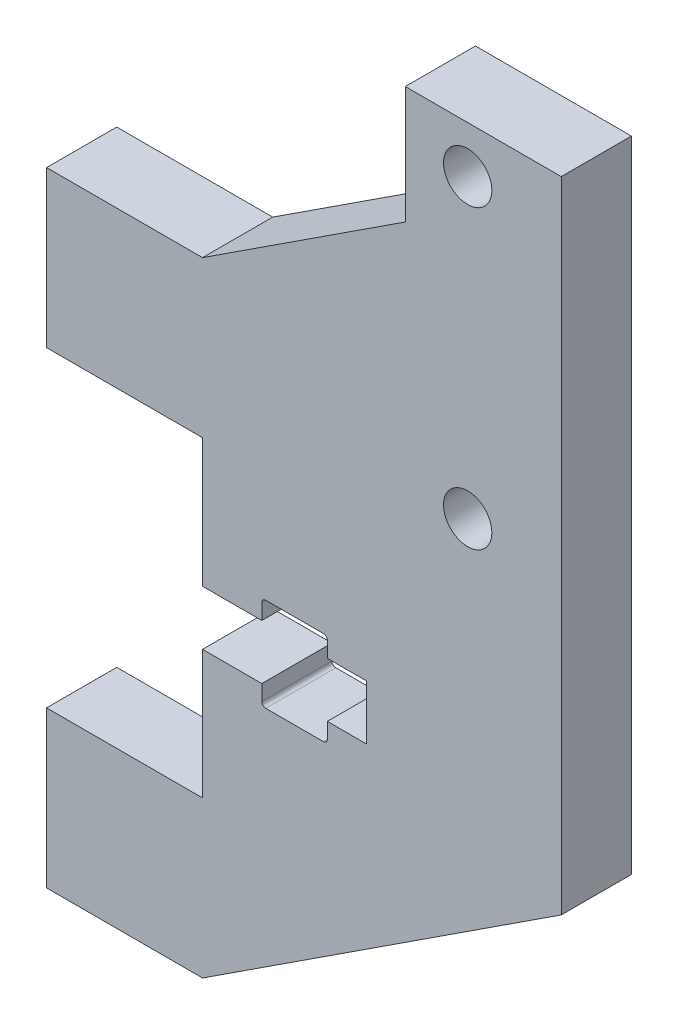
SolidWorks part; units mm, degrees
ref_plane "Front Plane" through (0, 0, 0) normal (0, 0, 1) x (1, 0, 0)
ref_plane "Top Plane" through (0, 0, 0) normal (0, 1, 0) x (1, 0, 0)
ref_plane "Right Plane" through (0, 0, 0) normal (1, 0, 0) x (0, 0, -1)
sketch "Sketch1" plane through (0, 0, 0) normal (0, 0, 1) x (1, 0, 0)
  line L0 (13, 3.4783) -> (0, -5)
  line L1 (0, -5) -> (-10, -5)
  line L2 (-10, -5) -> (-10, -15)
  line L3 (-10, -15) -> (0, -15)
  line L4 (0, -15) -> (0, -35)
  line L5 (0, -35) -> (-10, -35)
  line L6 (-10, -35) -> (-10, -45)
  line L7 (-10, -45) -> (0, -45)
  line L10 (0, -45) -> (23, -30)
  line L11 (23, -30) -> (23, 11)
  line L12 (23, 11) -> (13, 11)
  line L13 (13, 11) -> (13, 3.4783)
  line L15 (0, -5) -> (0, -45) construction
  line L16 (-10, -10) -> (0, -10) construction
  line L17 (-10, -40) -> (0, -40) construction
  line L18 (-10, -15) -> (-10, -35) construction
  line L19 (-10, -25) -> (0, -25) construction
  dimension "D2" = 10
  dimension "D3" = 10
  dimension "D4" = 10
  dimension "D5" = 15
  dimension "D8" = 10
  dimension "D10" = 13
  dimension "D6" = 15
  dimension "D7" = 16
extrude "Boss-Extrude1" add sketch "Sketch1" along normal blind 4.5
sketch "Sketch2" plane through (0, 0, 4.5) normal (0, 0, 1) x (1, 0, 0)
  line L0 (0, -25) -> (23, -25) construction
  line L1 (0, -15) -> (0, -35) construction
  line L3 (10.5, -26.75) -> (10.5, -23.25) construction
  line L4 (10.5, -23.25) -> (0, -23.25) construction
  line L5 (0, -26.75) -> (0, -23.25)
  line L6 (0, -23.25) -> (3.8, -23.25)
  line L7 (3.8, -23.25) -> (3.8, -22.25)
  line L8 (4.05, -22) -> (7.75, -22)
  line L9 (8, -22.25) -> (8, -23.25)
  line L10 (8, -23.25) -> (10.5, -23.25)
  line L11 (10.5, -23.25) -> (10.5, -26.75)
  line L12 (10.5, -26.75) -> (0, -26.75) construction
  line L13 (8, -26.75) -> (10.5, -26.75)
  line L14 (8, -27.75) -> (8, -26.75)
  line L15 (4.05, -28) -> (7.75, -28)
  line L16 (3.8, -26.75) -> (3.8, -27.75)
  line L17 (0, -26.75) -> (3.8, -26.75)
  line L18 (23, -30) -> (23, 11) construction
  arc A0 (7.75, -22) -> (8, -22.25) centre (7.75, -22.25) cw
  arc A1 (3.8, -22.25) -> (4.05, -22) centre (4.05, -22.25) cw
  arc A2 (3.8, -27.75) -> (4.05, -28) centre (4.05, -27.75) ccw
  arc A3 (7.75, -28) -> (8, -27.75) centre (7.75, -27.75) ccw
  point P15 (8, -22)
  point P18 (3.8, -22)
  point P27 (10.5, -25)
  point P29 (3.8, -28)
  point P30 (8, -28)
  dimension "D6" = 0.25
  dimension "D1" = 10.5
  dimension "D2" = 1.75
  dimension "D3" = 8
  dimension "D4" = 4.2
  dimension "D5" = 3
extrude "screw-cutout" cut sketch "Sketch2" against normal through all
sketch "Sketch3" plane through (0, 0, 4.5) normal (0, 0, 1) x (1, 0, 0)
  line L0 (17, 55) -> (17, -45) construction
  line L3 (13, 11) -> (13, 3.4783) construction
  line L5 (-10, -45) -> (0, -45) construction
  line L10 (10.5, -26.75) -> (10.5, -23.25) construction
  circle A1 centre (17, 8) radius 1.55
  circle A5 centre (17, -11) radius 1.55
  point P8 (10.5, -25)
  dimension "D4" = 3.1
  dimension "D11" = 3.1
  dimension "D6" = 4
  dimension "D12" = 19
  dimension "D2" = 14
extrude "Cut-Extrude2" cut sketch "Sketch3" against normal through all
sketch "Sketch4" plane through (0, 0, 4.5) normal (0, 0, 1) x (1, 0, 0)
  line L0 (17, -11) -> (17, 8) construction
  line L1 (17, -1.5) -> (13, -1.5) construction
  line L2 (13, 11) -> (13, 3.4783) construction
  line L4 (15, 2.5) -> (13, 2.5)
  line L5 (15, 2.5) -> (15, -5.5)
  line L6 (15, -5.5) -> (13, -5.5)
  line L7 (13, 2.5) -> (13, -5.5)
  line L8 (15, 2.5) -> (13, -5.5) construction
  line L9 (15, -5.5) -> (13, 2.5) construction
  circle A1 centre (17, 8) radius 1.55 construction
  circle A3 centre (17, -11) radius 1.55 construction
  point P11 (14, -1.5)
  dimension "D1" = 8
  dimension "D2" = 2
  dimension "D3" = 3
equation "\"X-ROD-SPACING\"=45"
equation "\"Y-ROD-SPACING\"=75"
equation "\"Z-ROD-SPACING\"=17.5"
equation "\"Y-BED-OFFSET\"=2"
equation "\"Y-BED-ROD-INSET\"=3.5"
equation "\"T-SLOT-NUT-FILLET-RADIUS\"=0.25"
equation "\"T-SLOT-SCREW-SHAFT-RADIUS\"=1.75"
equation "\"T-SLOT-SCREW-SHAFT-CUTOUT-LENGTH\"=10.5"
equation "\"T-SLOT-NUT-DEPTH\"=4.2"
equation "\"T-SLOT-NUT-WIDTH\"=3"
equation "\"T-SLOT-NUT-END-DISTANCE\"=8"
equation "\"ACRYLIC-THICKNESS\"=10"
equation "\"ACRYLIC-THICKNESS2\"=4.5"
equation "\"ACRYLIC-TAB-CUTOUT-SIZE\"=\"ACRYLIC-THICKNESS\"+\"ACRYLIC-TAB-TOLERANCE\"*2"
equation "\"ACRYLIC-TAB-WIDTH\"=\"ACRYLIC-THICKNESS\""
equation "\"ACRYLIC-M3-HOLE\"=3.1"
equation "\"SMOOTHROD-CAP-SCREW-DISTANCE\"=20"
equation "\"FRAME-WIDTH-INNER\"=370"
equation "\"NEMA17-HOLE-SPACING\"=31"
equation "\"NEMA17-CENTRAL-CUTOUT\"=22.5"
equation "\"Z-BRACKET-REACH\"=55"
equation "\"Z-ROD-INSET\"=16"
equation "\"TOP-BRACKET-SPACING\"=40"
equation "\"SMOOTHROD-X-LENGTH\"=350"
equation "\"SMOOTHROD-Y-LENGTH\"=350"
equation "\"SMOOTHROD-Z-LENGTH\"=350"
equation "\"SMOOTHROD-TIGHTENING-HEADROOM\"=.25"
equation "\"LEADSCREW-Z-LENGTH\"=300"
equation "\"SCREW-LENGTH-FRAME\"=\"ACRYLIC-THICKNESS\" + 10"
equation "\"SCREW-HEAD-RADIUS\"=6"
equation "\"PRINTED-X-SMOOTHROD-DIAMETER\"=8.2"
equation "\"PRINTED-X-SMOOTHROD-CUTOUT\"=10"
equation "\"PRINTED-X-BASE-HEIGHT\"=10"
equation "\"PRINTED-LM8UU-CUTOUT-SIZE\"=15.25"
equation "\"PRINTED-LM8UU-CUTOUT-LENGTH\"=24.5"
equation "\"PRINTED-X-IDLER-HEIGHT\"=16"
equation "\"PSU-MOUNTING-WIDTH\"=95"
equation "\"PSU-MOUNTING-HEIGHT\"=177"
equation "\"Y-BELT-TO-ROD-DISTANCE\"=20"
equation "\"SPOOL-HOLDER-ROD-SPACING\"=150"
equation "\"D1@Sketch1\"=\"ACRYLIC-TAB-WIDTH\""
equation "\"D2@Sketch1\"=\"ACRYLIC-TAB-WIDTH\""
equation "\"D3@Sketch1\"=\"ACRYLIC-THICKNESS\""
equation "\"D4@Sketch1\"=\"ACRYLIC-THICKNESS\""
equation "\"D1@Boss-Extrude1\"=\"ACRYLIC-THICKNESS2\""
equation "\"D1@Sketch2\"=\"T-SLOT-SCREW-SHAFT-CUTOUT-LENGTH\""
equation "\"D2@Sketch2\"=\"T-SLOT-SCREW-SHAFT-RADIUS\""
equation "\"D3@Sketch2\"=\"T-SLOT-NUT-END-DISTANCE\""
equation "\"D4@Sketch2\"=\"T-SLOT-NUT-DEPTH\""
equation "\"D5@Sketch2\"=\"T-SLOT-NUT-WIDTH\""
equation "\"D6@Sketch2\"=\"T-SLOT-NUT-FILLET-RADIUS\""
equation "\"D4@Sketch3\"=\"ACRYLIC-M3-HOLE\""
equation "\"D11@Sketch3\"=\"ACRYLIC-M3-HOLE\""
equation "\"Y-BED-SCREW-SPACING\"=209"
equation "\"Y-BED-SCREW-CUTOUT-SLOT-HEIGHT\"=2"
equation "\"ACRYLIC-TAB-TOLERANCE\"=.1"
equation "\"SCREW-LENGTH-MOTOR\"=\"ACRYLIC-THICKNESS\" + 5"
equation "\"SCREW-LENGTH-EXTRUDER\"=28"
equation "\"PRINTED-M3-HOLE\"=3.5"
equation "\"ACRYLIC-X-CARRIAGE-WIDTH\"=55"
equation "\"ACRYLIC-X-CARRIAGE-HEIGHT\"=75"
equation "\"ACRYLIC-X-CARRIAGE-LM8UU-CUTOUT-WIDTH\"=24.25"
equation "\"ACRYLIC-X-CARRIAGE-LM8UU-CUTOUT-HEIGHT\"=11.5"
equation "\"ACRYLIC-X-CARRIAGE-SCREW-SPACING-X\"=15"
equation "\"ACRYLIC-X-CARRIAGE-SCREW-SPACING-Y\"=33"
equation "\"ACRYLIC-X-CARRIAGE-CENTER-TAB-SPACING\"=14"
equation "\"ACRYLIC-X-CARRIAGE-EXTRUDER-OFFSET\"=26"
equation "\"ACRYLIC-X-CARRIAGE-EXTRUDER-ANGLE\"=90"
equation "\"ACRYLIC-X-CARRIAGE-EXTRUDER-SHELF-DEPTH\"=\"ACRYLIC-X-CARRIAGE-EXTRUDER-OFFSET\" + 28"
equation "\"ACRYLIC-X-CARRIAGE-EXTRUDER-BRACE-SPACING\"=23"
equation "\"ACRYLIC-X-CARRIAGE-EXTRUDER-BRACE-TAB-OFFSET\"=20"
equation "\"ACRYLIC-X-CARRIAGE-EXTRUDER-BRACE-HEIGHT\"=35"
equation "\"ACRYLIC-X-CARRIAGE-EXTRUDER-BRACE-SCREW-SPACING\"=22"
equation "\"ACRYLIC-X-CARRIAGE-DUAL-WIDTH-MULTIPLIER\"=1.65"
equation "\"ACRYLIC-X-CARRIAGE-DUAL-HOTEND-SPACING\"=42"
equation "\"ACRYLIC-X-CARRIAGE-DUAL-WIDTH\"=95"
equation "\"ACRYLIC-X-CARRIAGE-DUAL-HOTEND-SEPARATION\"=35"
equation "\"ACRYLIC-X-CARRIAGE-DUAL-MOUNT-PLATE-DEPTH\"=75"
equation "\"ACRYLIC-X-CARRIAGE-DUAL-MOUNT-BRACE-WIDTH\"=33"
equation "\"ACRYLIC-X-CARRIAGE-DUAL-MOUNT-SCREW-WIDTH\"=40"
equation "\"BLOWER-FAN-WIDTH\"=15"
